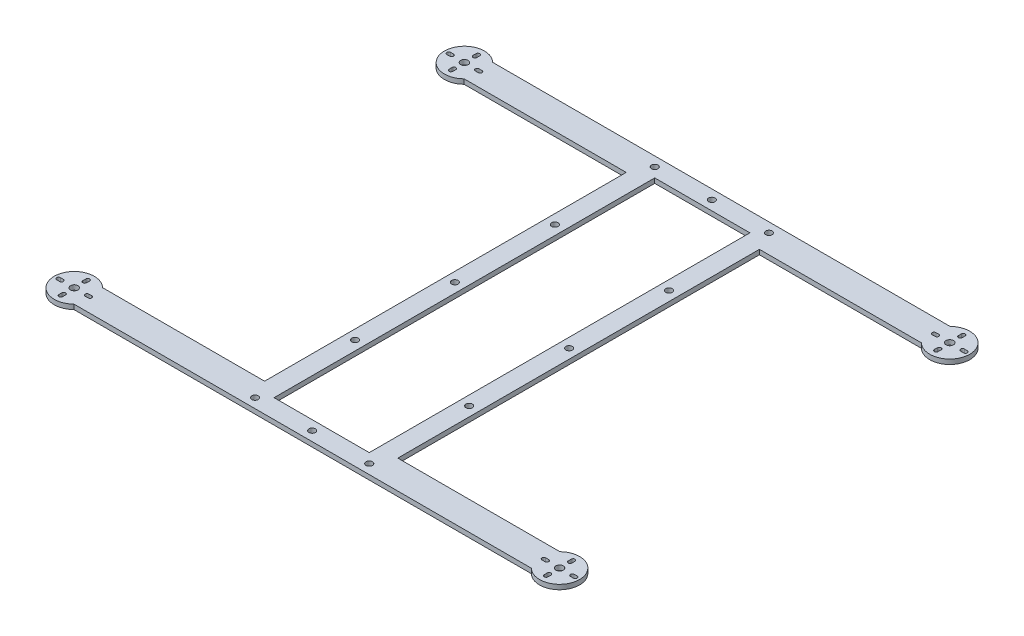
SolidWorks part; units mm, degrees
ref_plane "Front Plane" through (0, 0, 0) normal (0, 0, 1) x (1, 0, 0)
ref_plane "Top Plane" through (0, 0, 0) normal (0, 1, 0) x (1, 0, 0)
ref_plane "Right Plane" through (0, 0, 0) normal (1, 0, 0) x (0, 0, -1)
sketch "Sketch1" plane through (0, 0, 0) normal (0, 1, 0) x (1, 0, 0)
  line L1 (-44.45, 139.7) -> (44.45, 139.7)
  line L2 (-44.45, 120.65) -> (-44.45, -120.65)
  line L3 (-44.45, -139.7) -> (44.45, -139.7)
  line L4 (44.45, 120.65) -> (44.45, -120.65)
  line L5 (44.45, 139.7) -> (161.925, 139.7)
  line L7 (44.45, 120.65) -> (161.925, 120.65)
  line L8 (161.925, 139.7) -> (161.925, 120.65)
  line L14 (0, 0) -> (0, 187.5455) construction
  line L17 (0, 0) -> (-239.6804, 0) construction
  line L21 (0, 0) -> (44.45, 0) construction
  line L22 (-44.45, 120.65) -> (-161.925, 120.65)
  line L23 (-44.45, 139.7) -> (-161.925, 139.7)
  line L24 (-161.925, 139.7) -> (-161.925, 120.65)
  line L37 (-31.75, 127) -> (31.75, 127)
  line L40 (-31.75, 127) -> (-31.75, -127)
  line L43 (-31.75, -127) -> (31.75, -127)
  line L46 (31.75, 127) -> (31.75, -127)
  line L49 (44.45, -120.65) -> (161.925, -120.65)
  line L50 (44.45, -139.7) -> (161.925, -139.7)
  line L51 (161.925, -139.7) -> (161.925, -120.65)
  line L88 (-161.925, -139.7) -> (-161.925, -120.65)
  line L89 (-44.45, -139.7) -> (-161.925, -139.7)
  line L90 (-44.45, -120.65) -> (-161.925, -120.65)
  point P4 (0, 139.7)
  point P6 (-44.45, 0)
  dimension "D4" = 117.475
  dimension "D1" = 279.4
  dimension "D2" = 88.9
  dimension "D3" = 19.05
  dimension "D6" = 12.7
  dimension "D7" = 12.7
  dimension "D8" = 12.7
  dimension "D10" = 117.475
  dimension "D12" = 12.7
  dimension "D18" = 19.05
extrude "Boss-Extrude1" add sketch "Sketch1" along normal blind 3.175
sketch "Sketch4" plane through (0, 3.175, 0) normal (0, 1, 0) x (1, 0, 0)
  line L0 (161.925, 120.65) -> (161.925, 139.7) construction
  line L1 (-161.925, 139.7) -> (-161.925, 120.65) construction
  line L2 (-161.925, -120.65) -> (-161.925, -139.7) construction
  line L3 (161.925, -139.7) -> (161.925, -120.65) construction
  circle A0 centre (161.925, 130.175) radius 13.335
  circle A1 centre (-161.925, 130.175) radius 13.335
  circle A2 centre (-161.925, -130.175) radius 13.335
  circle A3 centre (161.925, -130.175) radius 13.335
  point P18 (161.925, -130.175)
extrude "Boss-Extrude4" add sketch "Sketch4" against normal up to surface (3.175 mm away) up to face at (0, 0, 0)
sketch "Sketch5" plane through (0, 3.175, 0) normal (0, 1, 0) x (1, 0, 0)
  line L0 (151.425, 130.175) -> (153.425, 130.175) construction
  line L1 (151.425, 131.425) -> (153.425, 131.425)
  line L2 (151.425, 128.925) -> (153.425, 128.925)
  line L3 (161.925, 130.175) -> (161.925, 143.51) construction
  line L4 (172.425, 130.175) -> (170.425, 130.175) construction
  line L5 (172.425, 131.425) -> (170.425, 131.425)
  line L6 (172.425, 128.925) -> (170.425, 128.925)
  line L7 (161.925, 139.175) -> (161.925, 137.175) construction
  line L8 (163.175, 139.175) -> (163.175, 137.175)
  line L9 (160.675, 139.175) -> (160.675, 137.175)
  line L10 (161.925, 130.175) -> (175.26, 130.175) construction
  line L11 (161.925, 121.175) -> (161.925, 123.175) construction
  line L12 (163.175, 121.175) -> (163.175, 123.175)
  line L13 (160.675, 121.175) -> (160.675, 123.175)
  line L14 (0, 0) -> (0, 263.0018) construction
  line L15 (0, 0) -> (558.7896, 0) construction
  line L16 (-151.425, 130.175) -> (-153.425, 130.175) construction
  line L17 (-151.425, 131.425) -> (-153.425, 131.425)
  line L18 (-151.425, 128.925) -> (-153.425, 128.925)
  line L19 (-172.425, 130.175) -> (-170.425, 130.175) construction
  line L20 (-172.425, 131.425) -> (-170.425, 131.425)
  line L21 (-172.425, 128.925) -> (-170.425, 128.925)
  line L22 (-161.925, 139.175) -> (-161.925, 137.175) construction
  line L23 (-163.175, 139.175) -> (-163.175, 137.175)
  line L24 (-160.675, 139.175) -> (-160.675, 137.175)
  line L25 (-161.925, 121.175) -> (-161.925, 123.175) construction
  line L26 (-163.175, 121.175) -> (-163.175, 123.175)
  line L27 (-160.675, 121.175) -> (-160.675, 123.175)
  line L28 (-161.925, 130.175) -> (-175.26, 130.175) construction
  line L29 (-161.925, 130.175) -> (-161.925, 143.51) construction
  line L30 (151.425, -130.175) -> (153.425, -130.175) construction
  line L31 (151.425, -131.425) -> (153.425, -131.425)
  line L32 (151.425, -128.925) -> (153.425, -128.925)
  line L33 (161.925, -139.175) -> (161.925, -137.175) construction
  line L34 (163.175, -139.175) -> (163.175, -137.175)
  line L35 (160.675, -139.175) -> (160.675, -137.175)
  line L36 (172.425, -130.175) -> (170.425, -130.175) construction
  line L37 (172.425, -131.425) -> (170.425, -131.425)
  line L38 (172.425, -128.925) -> (170.425, -128.925)
  line L39 (161.925, -121.175) -> (161.925, -123.175) construction
  line L40 (163.175, -121.175) -> (163.175, -123.175)
  line L41 (160.675, -121.175) -> (160.675, -123.175)
  line L42 (161.925, -130.175) -> (175.26, -130.175) construction
  line L43 (161.925, -130.175) -> (161.925, -143.51) construction
  line L44 (-161.925, -130.175) -> (-161.925, -143.51) construction
  line L45 (-161.925, -130.175) -> (-175.26, -130.175) construction
  line L46 (-161.925, -121.175) -> (-161.925, -123.175) construction
  line L47 (-163.175, -121.175) -> (-163.175, -123.175)
  line L48 (-160.675, -121.175) -> (-160.675, -123.175)
  line L49 (-161.925, -139.175) -> (-161.925, -137.175) construction
  line L50 (-163.175, -139.175) -> (-163.175, -137.175)
  line L51 (-160.675, -139.175) -> (-160.675, -137.175)
  line L52 (-172.425, -130.175) -> (-170.425, -130.175) construction
  line L53 (-172.425, -131.425) -> (-170.425, -131.425)
  line L54 (-172.425, -128.925) -> (-170.425, -128.925)
  line L55 (-151.425, -130.175) -> (-153.425, -130.175) construction
  line L56 (-151.425, -131.425) -> (-153.425, -131.425)
  line L57 (-151.425, -128.925) -> (-153.425, -128.925)
  circle A0 centre (161.925, 130.175) radius 2.5
  arc A1 (151.425, 131.425) -> (151.425, 128.925) centre (151.425, 130.175) ccw
  arc A2 (153.425, 128.925) -> (153.425, 131.425) centre (153.425, 130.175) ccw
  arc A3 (152.5924, 120.65) -> (152.5924, 139.7) centre (161.925, 130.175) ccw construction
  arc A4 (172.425, 131.425) -> (172.425, 128.925) centre (172.425, 130.175) cw
  arc A5 (170.425, 128.925) -> (170.425, 131.425) centre (170.425, 130.175) cw
  arc A6 (163.175, 139.175) -> (160.675, 139.175) centre (161.925, 139.175) ccw
  arc A7 (160.675, 137.175) -> (163.175, 137.175) centre (161.925, 137.175) ccw
  arc A8 (163.175, 121.175) -> (160.675, 121.175) centre (161.925, 121.175) cw
  arc A9 (160.675, 123.175) -> (163.175, 123.175) centre (161.925, 123.175) cw
  arc A10 (-151.425, 131.425) -> (-151.425, 128.925) centre (-151.425, 130.175) cw
  arc A11 (-153.425, 128.925) -> (-153.425, 131.425) centre (-153.425, 130.175) cw
  arc A12 (-172.425, 131.425) -> (-172.425, 128.925) centre (-172.425, 130.175) ccw
  arc A13 (-170.425, 128.925) -> (-170.425, 131.425) centre (-170.425, 130.175) ccw
  arc A14 (-163.175, 139.175) -> (-160.675, 139.175) centre (-161.925, 139.175) cw
  arc A15 (-160.675, 137.175) -> (-163.175, 137.175) centre (-161.925, 137.175) cw
  arc A16 (-163.175, 121.175) -> (-160.675, 121.175) centre (-161.925, 121.175) ccw
  arc A17 (-160.675, 123.175) -> (-163.175, 123.175) centre (-161.925, 123.175) ccw
  circle A18 centre (-161.925, 130.175) radius 2.5
  arc A19 (151.425, -131.425) -> (151.425, -128.925) centre (151.425, -130.175) cw
  arc A20 (153.425, -128.925) -> (153.425, -131.425) centre (153.425, -130.175) cw
  arc A21 (163.175, -139.175) -> (160.675, -139.175) centre (161.925, -139.175) cw
  arc A22 (160.675, -137.175) -> (163.175, -137.175) centre (161.925, -137.175) cw
  arc A23 (172.425, -131.425) -> (172.425, -128.925) centre (172.425, -130.175) ccw
  arc A24 (170.425, -128.925) -> (170.425, -131.425) centre (170.425, -130.175) ccw
  arc A25 (163.175, -121.175) -> (160.675, -121.175) centre (161.925, -121.175) ccw
  arc A26 (160.675, -123.175) -> (163.175, -123.175) centre (161.925, -123.175) ccw
  circle A27 centre (161.925, -130.175) radius 2.5
  circle A28 centre (-161.925, -130.175) radius 2.5
  arc A29 (-163.175, -121.175) -> (-160.675, -121.175) centre (-161.925, -121.175) cw
  arc A30 (-160.675, -123.175) -> (-163.175, -123.175) centre (-161.925, -123.175) cw
  arc A31 (-163.175, -139.175) -> (-160.675, -139.175) centre (-161.925, -139.175) ccw
  arc A32 (-160.675, -137.175) -> (-163.175, -137.175) centre (-161.925, -137.175) ccw
  arc A33 (-172.425, -131.425) -> (-172.425, -128.925) centre (-172.425, -130.175) cw
  arc A34 (-170.425, -128.925) -> (-170.425, -131.425) centre (-170.425, -130.175) cw
  arc A35 (-151.425, -131.425) -> (-151.425, -128.925) centre (-151.425, -130.175) ccw
  arc A36 (-153.425, -128.925) -> (-153.425, -131.425) centre (-153.425, -130.175) ccw
  point P5 (152.425, 130.175)
  point P16 (171.425, 130.175)
  point P23 (161.925, 138.175)
  point P31 (161.925, 122.175)
  point P42 (-152.425, 130.175)
  point P49 (-171.425, 130.175)
  point P56 (-161.925, 138.175)
  point P63 (-161.925, 122.175)
  point P74 (152.425, -130.175)
  point P81 (161.925, -138.175)
  point P88 (171.425, -130.175)
  point P95 (161.925, -122.175)
  point P110 (-161.925, -122.175)
  point P117 (-161.925, -138.175)
  point P124 (-171.425, -130.175)
  point P131 (-152.425, -130.175)
  point P136 (0, 0)
  point P137 (0, 0)
  dimension "D1" = 5
  dimension "D2" = 2.5
  dimension "D3" = 2
  dimension "D4" = 19
  dimension "D5" = 2.5
  dimension "D6" = 2
  dimension "D7" = 16
extrude "Motor Holes" cut sketch "Sketch5" against normal through all
sketch "Sketch7" plane through (0, 3.175, 0) normal (0, 1, 0) x (1, 0, 0)
  line L0 (152.5924, 139.7) -> (-152.5924, 139.7) construction
  line L1 (-44.45, 120.65) -> (-44.45, -120.65) construction
  line L2 (0, 0) -> (0, 246.0772) construction
  line L3 (0, 0) -> (301.4392, 0) construction
  circle A0 centre (-38.1, 133.35) radius 2.159
  circle A1 centre (-38.1, 66.675) radius 2.159
  circle A2 centre (-38.1, 0) radius 2.159
  circle A3 centre (-38.1, -66.675) radius 2.159
  circle A5 centre (-38.1, -133.35) radius 2.159
  circle A6 centre (38.1, -133.35) radius 2.159
  circle A7 centre (38.1, -66.675) radius 2.159
  circle A8 centre (38.1, 0) radius 2.159
  circle A9 centre (38.1, 66.675) radius 2.159
  circle A10 centre (38.1, 133.35) radius 2.159
  circle A11 centre (0, 133.35) radius 2.159
  circle A12 centre (0, -133.35) radius 2.159
  dimension "D1" = 4.318
  dimension "D2" = 6.35
  dimension "D3" = 6.35
  dimension "D4" = 66.675
  dimension "D5" = 66.675
  dimension "D6" = 66.675
  dimension "D7" = 66.675
extrude "Cut-Extrude2" cut sketch "Sketch7" against normal through all
